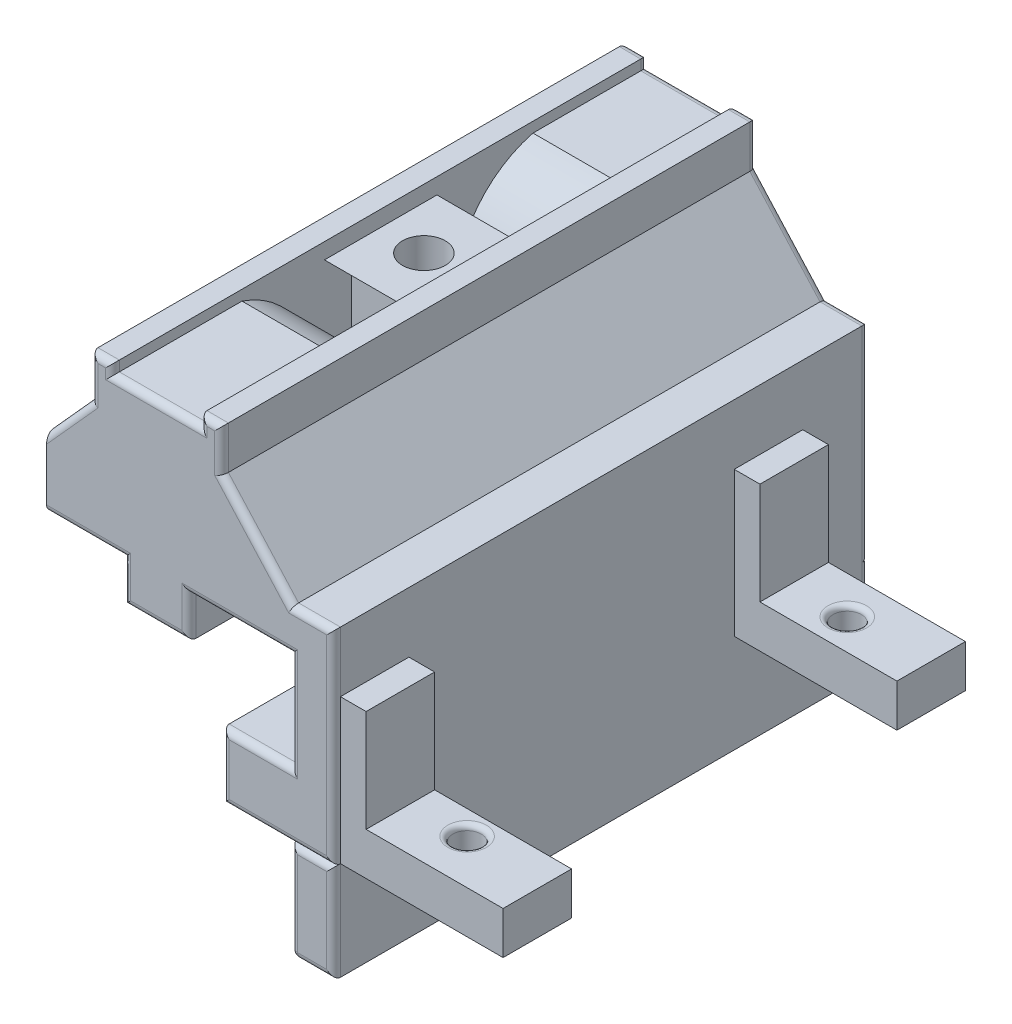
SolidWorks part; units mm, degrees
ref_plane "Front" through (0, 0, 0) normal (0, 0, 1) x (1, 0, 0)
ref_plane "Top" through (0, 0, 0) normal (0, 1, 0) x (1, 0, 0)
ref_plane "Right" through (0, 0, 0) normal (1, 0, 0) x (0, 0, -1)
sketch "Sketch2" plane through (0, 0, 0) normal (0, 0, 1) x (1, 0, 0)
  line L0 (-4.895, 3.0291) -> (-9.97, 3.0291)
  line L1 (-9.97, 3.0291) -> (-9.97, 10.3311)
  line L2 (-9.97, 10.3311) -> (-2.42, 10.3311)
  line L3 (-2.42, 10.3311) -> (-2.42, 7.2831)
  line L4 (-2.42, 7.2831) -> (2.42, 7.2831)
  line L5 (0, -13.7255) -> (0, 13.7255) construction
  line L6 (-4.895, 3.0291) -> (-4.895, -1.8209)
  line L7 (-4.895, -1.8209) -> (-13.145, -1.8209)
  line L8 (-13.145, -1.8209) -> (-13.145, 13.3791)
  line L9 (-13.145, 13.3791) -> (-10.045, 13.3791)
  line L10 (-10.045, 13.3791) -> (-4.8375, 19.1576)
  line L11 (-4.8375, 19.1576) -> (-4.8375, 22.3326)
  line L12 (-4.8375, 22.3326) -> (-3.25, 22.3326)
  line L13 (-3.25, 22.3326) -> (-3.25, 21.5706)
  line L14 (-3.25, 21.5706) -> (3.25, 21.5706)
  line L15 (3.25, 22.3326) -> (3.25, 21.5706)
  line L16 (4.8375, 22.3326) -> (3.25, 22.3326)
  line L17 (4.8375, 19.1576) -> (4.8375, 22.3326)
  line L18 (10.045, 13.3791) -> (4.8375, 19.1576)
  line L19 (13.145, 13.3791) -> (10.045, 13.3791)
  line L20 (13.145, -1.8209) -> (13.145, 13.3791)
  line L21 (4.895, -1.8209) -> (13.145, -1.8209)
  line L22 (4.895, 3.0291) -> (4.895, -1.8209)
  line L23 (2.42, 10.3311) -> (2.42, 7.2831)
  line L24 (9.97, 10.3311) -> (2.42, 10.3311)
  line L25 (9.97, 3.0291) -> (9.97, 10.3311)
  line L26 (4.895, 3.0291) -> (9.97, 3.0291)
  point P23 (0, 21.5706)
  point P32 (0, 7.2831)
  dimension "D1" = 4.85
  dimension "D2" = 8.25
  dimension "D3" = 3.175
  dimension "D4" = 15.2
  dimension "D5" = 3.048
  dimension "D6" = 3.048
  dimension "D7" = 14.2875
  dimension "D8" = 3.175
  dimension "D9" = 0.762
  dimension "D10" = 1.5875
  dimension "D11" = 3.25
  dimension "D12" = 3.1
  dimension "D13" = 7.55
  dimension "D14" = 2.42
extrude "Boss-Extrude1" add sketch "Sketch2" along normal blind 39.6875
sketch "Sketch3" plane through (0, 21.5706, 0) normal (0, 1, 0) x (1, 0, 0)
  line L0 (0, 0) -> (0, -39.6875) construction
  line L1 (-13.145, -19.8438) -> (13.145, -19.8438) construction
  line L2 (-13.145, -39.6875) -> (-13.145, 0) construction
  line L3 (13.145, -39.6875) -> (13.145, 0) construction
  line L4 (3.25, 0) -> (-3.25, 0)
  line L5 (-3.25, 0) -> (-3.25, -39.6875)
  line L6 (-3.25, -39.6875) -> (3.25, -39.6875)
  line L7 (3.25, -39.6875) -> (3.25, 0)
  line L8 (3.25, 0) -> (-3.25, 0)
  line L9 (-3.25, 0) -> (-3.25, -39.6875)
  line L10 (-3.25, -39.6875) -> (3.25, -39.6875)
  line L11 (3.25, -39.6875) -> (3.25, 0)
  circle A0 centre (0, -19.8437) radius 1.5875
  dimension "D2" = 3.175
  dimension "D1" = 0
extrude "Cut-Extrude1" cut sketch "Sketch3" against normal blind 39.6875 contours A0
sketch "Sketch4" plane through (0, 7.2831, 0) normal (0, -1, 0) x (1, 0, 0)
  line L1 (1.7609, 16.7937) -> (3.5218, 19.8438)
  line L2 (3.5218, 19.8438) -> (1.7609, 22.8937)
  line L3 (1.7609, 22.8937) -> (-1.7609, 22.8937)
  line L4 (-2.42, 0) -> (2.42, 0)
  line L5 (2.42, 0) -> (2.42, 39.6875)
  line L6 (2.42, 39.6875) -> (-2.42, 39.6875)
  line L8 (-2.42, 0) -> (2.42, 0)
  line L9 (2.42, 0) -> (2.42, 39.6875)
  line L12 (-1.7609, 22.8937) -> (-3.5218, 19.8437)
  line L13 (-3.5218, 19.8437) -> (-1.7609, 16.7937)
  line L14 (-1.7609, 16.7937) -> (1.7609, 16.7937)
  line L18 (2.42, 39.6875) -> (-2.42, 39.6875)
  line L20 (-2.42, 39.6875) -> (-2.42, 0)
  line L21 (-2.42, 39.6875) -> (-2.42, 0)
  circle A0 centre (0, 19.8437) radius 3.05 construction
  circle M11 centre (0, 19.8437) radius 1.5875
  dimension "D2" = 6.1
  dimension "D1" = 0
extrude "Cut-Extrude3" cut sketch "Sketch4" against normal blind 5 contours M11 | L12 L13 M11 | L13 L14 M11 | L14 L1 M11 | L1 L2 M11 | L2 L3 M11 | L3 L12 M11
sketch "Sketch5" plane through (-2.42, 0, 0) normal (-1, 0, 0) x (0, 0, 1)
  line L0 (21.967, 7.1576) -> (21.967, 19.1576)
  line L6 (30.9394, 21.8041) -> (6.7522, 21.8041)
  line L9 (39.6875, 19.1576) -> (0, 19.1576) construction
  line L12 (9.474, 7.1576) -> (17.626, 7.1576)
  line L18 (21.967, 7.1576) -> (30.1191, 7.1576)
  line L23 (17.626, 7.1576) -> (17.626, 19.1576)
  line L24 (17.626, 19.1576) -> (15.626, 21.1576)
  line L25 (21.967, 19.1576) -> (23.967, 21.1576)
  line L26 (15.626, 21.1576) -> (23.967, 21.1576)
  arc A0 (30.9394, 21.8041) -> (30.1191, 7.1576) centre (32.5165, 14.3696) ccw
  arc A1 (6.7522, 21.8041) -> (9.474, 7.1576) centre (6.6292, 14.2051) cw
  dimension "D2" = 45
  dimension "D3" = 7.6
  dimension "D1" = 7.6
  dimension "D4" = 2
  dimension "D5" = 12
  dimension "D6" = 8.1521
  dimension "D7" = 4.3409
extrude "Cut-Extrude5" cut sketch "Sketch5" against normal blind 5.67 and the other way blind 0.83
sketch "Sketch6" plane through (-3.25, 0, 0) normal (1, 0, 0) x (0, 0, -1)
  line L0 (-26.3863, 10.5206) -> (-13.2066, 10.5206)
  line L1 (-9.474, 7.2831) -> (-30.1189, 7.2831)
fillet "Fillet1" radius 0.508 52 edges at (-7.4325, 3.0291, 0) (-9.97, 6.6801, 0) (6.195, 10.3311, 0) (-2.42, 8.8071, 0) (0, 7.2831, 0) (2.42, 8.8071, 0) (9.97, 6.6801, 0) (7.4325, 3.0291, 0) (4.895, 0.6041, 0) (9.02, -1.8209, 0) (13.145, 5.7791, 0) (11.595, 13.3791, 0) (7.4412, 16.2684, 0) (4.8375, 20.7451, 0) (4.0437, 22.3326, 0) (3.25, 21.9516, 0) (0, 21.5706, 0) (-3.25, 21.9516, 0) (-4.0437, 22.3326, 0) (-4.8375, 20.7451, 0) (-7.4412, 16.2684, 0) (-11.595, 13.3791, 0) (-13.145, 5.7791, 0) (-9.02, -1.8209, 0) (-4.895, 0.6041, 0) (-9.02, -1.8209, 39.6875) (-13.145, 5.7791, 39.6875) (-11.595, 13.3791, 39.6875) (-7.4412, 16.2684, 39.6875) (-4.8375, 20.7451, 39.6875) (-4.0437, 22.3326, 39.6875) (-3.25, 21.9516, 39.6875) (0, 21.5706, 39.6875) (3.25, 21.9516, 39.6875) (4.0437, 22.3326, 39.6875) (4.8375, 20.7451, 39.6875) (7.4412, 16.2684, 39.6875) (11.595, 13.3791, 39.6875) (13.145, 5.7791, 39.6875) (9.02, -1.8209, 39.6875) (4.895, 0.6041, 39.6875) (7.4325, 3.0291, 39.6875) (9.97, 6.6801, 39.6875) (6.195, 10.3311, 39.6875) (2.42, 8.8071, 39.6875) (0, 7.2831, 39.6875) (-2.42, 8.8071, 39.6875) (-9.97, 6.6801, 39.6875) (-7.4325, 3.0291, 39.6875) (-4.895, 0.6041, 39.6875) (-6.195, 10.3311, 0) (-6.195, 10.3311, 39.6875)
sketch "Sketch7" plane through (13.145, 0, 0) normal (1, 0, 0) x (0, 0, -1)
  line L0 (-39.1795, -1.8209) -> (-0.508, -1.8209) construction
  line L1 (-39.1795, -1.8209) -> (-34.0995, -1.8209)
  line L2 (-39.1795, -1.8209) -> (-39.1795, 8.9054)
  line L3 (-39.1795, 8.9054) -> (-34.0995, 8.9054)
  line L4 (-34.0995, -1.8209) -> (-34.0995, 8.9054)
  line L5 (-9.9695, -1.8209) -> (-4.8895, -1.8209)
  line L6 (-9.9695, -1.8209) -> (-9.9695, 8.9054)
  line L7 (-9.9695, 8.9054) -> (-4.8895, 8.9054)
  line L8 (-4.8895, -1.8209) -> (-4.8895, 8.9054)
  dimension "D1" = 5.08
  dimension "D2" = 24.13
extrude "Boss-Extrude2" add sketch "Sketch7" along normal blind 1.905
sketch "Sketch8" plane through (15.05, 0, 0) normal (1, 0, 0) x (0, 0, -1)
  line L0 (-39.1795, 1.336) -> (-34.0995, 1.336)
  line L1 (-9.9695, 1.336) -> (-4.8895, 1.336)
  line L4 (-39.1795, 8.9054) -> (-39.1795, -1.8209)
  line L5 (-39.1795, -1.8209) -> (-34.0995, -1.8209)
  line L6 (-34.0995, -1.8209) -> (-34.0995, 8.9054)
  line L7 (-34.0995, 8.9054) -> (-39.1795, 8.9054)
  line L8 (-39.1795, 8.9054) -> (-39.1795, -1.8209)
  line L9 (-39.1795, -1.8209) -> (-34.0995, -1.8209)
  line L10 (-34.0995, -1.8209) -> (-34.0995, 8.9054)
  line L11 (-34.0995, 8.9054) -> (-39.1795, 8.9054)
  line L12 (-9.9695, 8.9054) -> (-9.9695, -1.8209)
  line L13 (-9.9695, -1.8209) -> (-4.8895, -1.8209)
  line L14 (-4.8895, -1.8209) -> (-4.8895, 8.9054)
  line L15 (-4.8895, 8.9054) -> (-9.9695, 8.9054)
  line L16 (-9.9695, 8.9054) -> (-9.9695, -1.8209)
  line L17 (-9.9695, -1.8209) -> (-4.8895, -1.8209)
  line L18 (-4.8895, -1.8209) -> (-4.8895, 8.9054)
  line L19 (-4.8895, 8.9054) -> (-9.9695, 8.9054)
  line M9 (-39.1795, 8.9054) -> (-39.1795, -1.8209)
  line M10 (-39.1795, -1.8209) -> (-34.0995, -1.8209)
  line M11 (-34.0995, -1.8209) -> (-34.0995, 8.9054)
  dimension "D1" = 0
  dimension "D2" = 0
extrude "Boss-Extrude3" add sketch "Sketch8" along normal blind 10.16 contours L0 M9 M10 M11 | L17 L18 L1 L16
sketch "Sketch9" plane through (0, -1.8209, 0) normal (0, -1, 0) x (1, 0, 0)
  line L11 (4.895, 39.1795) -> (4.895, 0.508)
  line L12 (4.895, 0.508) -> (13.145, 0.508)
  line L13 (13.145, 0.508) -> (13.145, 4.8895)
  line L14 (13.145, 4.8895) -> (25.21, 4.8895)
  line L15 (25.21, 4.8895) -> (25.21, 9.9695)
  line L16 (25.21, 9.9695) -> (13.145, 9.9695)
  line L17 (13.145, 9.9695) -> (13.145, 34.0995)
  line L18 (13.145, 34.0995) -> (25.21, 34.0995)
  line L19 (25.21, 34.0995) -> (25.21, 39.1795)
  line L20 (25.21, 39.1795) -> (13.145, 39.1795)
  line L21 (13.145, 39.1795) -> (4.895, 39.1795)
  line L22 (4.895, 39.1795) -> (4.895, 0.508)
  line L23 (4.895, 0.508) -> (13.145, 0.508)
  line L24 (13.145, 0.508) -> (13.145, 4.8895)
  line L25 (13.145, 4.8895) -> (25.21, 4.8895)
  line L26 (25.21, 4.8895) -> (25.21, 9.9695)
  line L27 (25.21, 9.9695) -> (13.145, 9.9695)
  line L28 (13.145, 9.9695) -> (13.145, 34.0995)
  line L29 (13.145, 34.0995) -> (25.21, 34.0995)
  line L30 (25.21, 34.0995) -> (25.21, 39.1795)
  line L31 (25.21, 39.1795) -> (13.145, 39.1795)
  line L32 (13.145, 39.1795) -> (4.895, 39.1795)
  circle A0 centre (19.241, 7.6835) radius 1.05
  circle A1 centre (19.241, 35.8775) radius 1.05
  dimension "D2" = 2.1
  dimension "D4" = 2.1
  dimension "D6" = 6.096
  dimension "D7" = 6.096
  dimension "D3" = 2.286
  dimension "D5" = 1.778
  dimension "D1" = 0
extrude "Cut-Extrude7" cut sketch "Sketch9" against normal up to next contours A1 | A0
fillet "Fillet2" radius 0.381 4 edges at (20.291, -1.8209, 7.6835) (20.291, -1.8209, 35.8775) (18.191, 1.336, 7.6835) (18.191, 1.336, 35.8775)
sketch "Sketch10" plane through (0, 0, 39.6875) normal (0, 0, 1) x (1, 0, 0)
  line L0 (-13.795, 16.5567) -> (-8.1401, 16.5567)
  line L1 (-4.1248, -4.3672) -> (-15.5018, -4.3672)
  line L2 (-4.1248, -4.3672) -> (-4.1248, 5.9243)
  line L3 (-4.1248, 5.9243) -> (-15.5018, 5.9243)
  line L4 (-15.5018, -4.3672) -> (-15.5018, 5.9243)
  line L5 (-13.795, 16.5567) -> (-15.5018, 16.5567)
  line L6 (-8.1401, 16.5567) -> (-8.1401, 5.9243)
  line L7 (-8.1401, 5.9243) -> (-15.5018, 5.9243)
  line L16 (-15.5018, 16.5567) -> (-15.5018, 5.9243)
extrude "Cut-Extrude8" cut sketch "Sketch10" against normal through all contours L16 L5 L0 L6 L7 | L4 L1 L2 L3
sketch "Sketch11" plane through (0, 0, 39.1795) normal (0, 0, 1) x (1, 0, 0)
  line L0 (2.42, 10.3311) -> (2.42, 7.2831) construction
  line L1 (13.145, -1.8209) -> (9.97, -1.8209)
  line L2 (13.145, -1.8209) -> (13.145, -9.1229)
  line L3 (13.145, -9.1229) -> (9.97, -9.1229)
  line L4 (9.97, -1.8209) -> (9.97, -9.1229)
  line L5 (13.145, -9.1229) -> (2.42, -9.1229)
  line L6 (13.145, -9.1229) -> (13.145, -12.1729)
  line L7 (13.145, -12.1729) -> (2.42, -12.1729)
  line L8 (2.42, -9.1229) -> (2.42, -12.1729)
  line L9 (9.97, 3.0291) -> (10.478, 2.5211)
  line L10 (10.478, 2.5211) -> (10.478, 10.8391)
  line L11 (10.478, 10.8391) -> (9.97, 10.3311)
  line L12 (9.97, 10.3311) -> (9.97, 3.0291)
  line L13 (9.97, 3.0291) -> (10.478, 2.5211)
  line L14 (10.478, 2.5211) -> (10.478, 10.8391)
  line L15 (10.478, 10.8391) -> (9.97, 10.3311)
  line L16 (9.97, 10.3311) -> (9.97, 3.0291)
  line L17 (-2.42, 7.2831) -> (-2.42, 10.3311) construction
  line L18 (2.42, -12.1729) -> (-2.42, -12.1729)
  line L19 (2.42, -12.1729) -> (2.42, -6.0729)
  line L20 (2.42, -6.0729) -> (-2.42, -6.0729)
  line L21 (-2.42, -12.1729) -> (-2.42, -6.0729)
  line L22 (-8.1401, 14.734) -> (-8.1401, 10.8391) construction
  line L25 (-2.42, -12.1729) -> (-8.1401, -12.1729)
  line L26 (-2.42, -12.1729) -> (-2.42, -9.1229)
  line L27 (-2.42, -9.1229) -> (-8.1401, -9.1229)
  line L28 (-8.1401, -12.1729) -> (-8.1401, -9.1229)
  dimension "D2" = 3.05
  dimension "D3" = 3.05
  dimension "D1" = 0
extrude "Boss-Extrude4" add sketch "Sketch11" against normal up to vertex (39.1795 mm away) and the other way up to surface (0.508 mm away) contours L1 L4 L3 L2 | L19 L18 L21 L20 | L26 L25 L28 L27 up to point (12.637, -1.3129, 0) other way up to face at (2.4083, 12.8181, 39.6875)
fillet "Fillet3" radius 0.508 9 edges at (11.5575, -9.1229, 39.6875) (9.97, -9.1229, 19.8438) (11.5575, -9.1229, 0) (9.97, -5.4719, 0) (13.145, -5.4719, 0) (13.145, -5.4719, 39.6875) (9.97, -5.4719, 39.6875) (11.5575, -1.8209, 39.6875) (11.5575, -1.8209, 0)
sketch "Sketch13" plane through (0, 7.2831, 0) normal (0, -1, 0) x (1, 0, 0)
  line L1 (-2.42, 17.626) -> (2.42, 17.626)
  line L2 (-2.42, 17.626) -> (-2.42, 21.967)
  line L3 (-2.42, 21.967) -> (2.42, 21.967)
  line L4 (2.42, 17.626) -> (2.42, 21.967)
extrude "Cut-Extrude10" cut sketch "Sketch13" against normal up to surface (3.048 mm away) up to face at (-3.4775, 10.3311, 19.7723)
